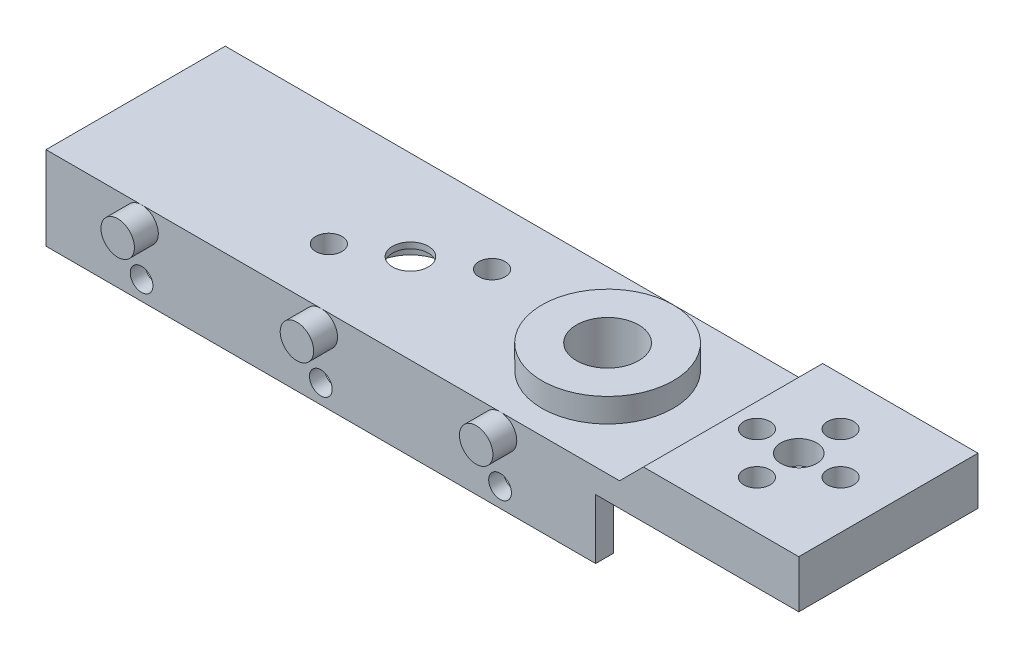
SolidWorks part; units mm, degrees
ref_plane "前视基准面" through (0, 0, 0) normal (0, 0, 1) x (1, 0, 0)
ref_plane "上视基准面" through (0, 0, 0) normal (0, 1, 0) x (1, 0, 0)
ref_plane "右视基准面" through (0, 0, 0) normal (1, 0, 0) x (0, 0, -1)
other "Configuration Table"
sketch "草图1" plane through (0, 0, 0) normal (0, 1, 0) x (1, 0, 0)
  line L0 (-31.5, 7.5) -> (31.5, 7.5)
  line L1 (31.5, 7.5) -> (31.5, -7.5)
  line L2 (31.5, -7.5) -> (-31.5, -7.5)
  line L3 (-31.5, -7.5) -> (-31.5, 7.5)
  line L4 (-31.5, 0) -> (31.5, 0) construction
  line L5 (-12.8301, -2.5) -> (-4.1699, 2.5) construction
  line L6 (-13.3083, -5.95) -> (-3.6917, -5.95) construction
  line L7 (-13.3083, 5.95) -> (-3.6917, 5.95) construction
  line L8 (-8.5, 0) -> (-8.5, 4.4384) construction
  line L10 (31.5, 7.5) -> (16.5, 7.5)
  line L11 (31.5, 7.5) -> (31.5, -7.5)
  line L12 (31.5, -7.5) -> (16.5, -7.5)
  line L13 (16.5, 7.5) -> (16.5, -7.5)
  circle A0 centre (-8.5, 0) radius 1.5
  circle A1 centre (-4.1699, 2.5) radius 1.1
  circle A3 centre (-12.8301, -2.5) radius 1.1
  arc A4 (-13.3083, 5.95) -> (-13.3083, -5.95) centre (-8.5, 0) ccw construction
  circle A5 centre (8, 0) radius 2.6
  arc A6 (-3.6917, -5.95) -> (-3.6917, 5.95) centre (-8.5, 0) ccw construction
  circle A7 centre (24, 0) radius 1.5
  circle A8 centre (24, 0) radius 3.5 construction
  circle A9 centre (27.5, 0) radius 1.1
  circle A10 centre (24, -3.5) radius 1.1
  circle A11 centre (20.5, 0) radius 1.1
  circle A12 centre (24, 3.5) radius 1.1
  circle A13 centre (-4.1699, -2.5) radius 1.1
  circle A14 centre (-12.8301, 2.5) radius 1.1
  circle A20 centre (24, 0) radius 6
  circle A21 centre (8, 0) radius 7
  point P5 (0, 7.5)
  point P7 (-31.5, 0)
  dimension "D3" = 3
  dimension "D6" = 2.2
  dimension "D9" = 15.3
  dimension "D12" = 5.2
  dimension "D14" = 3
  dimension "D15" = 7
  dimension "D16" = 2.2
  dimension "D22" = 12
  dimension "D23" = 14
  dimension "D1" = 63
  dimension "D2" = 15
  dimension "D4" = 23
  dimension "D7" = 30
  dimension "D8" = 10
  dimension "D10" = 11.9
  dimension "D11" = 16.5
  dimension "D13" = 16
  dimension "D21" = 15
  dimension "D5" = 2
  dimension "D17" = 4
extrude "凸台-拉伸1" add sketch "草图1" along normal blind 2
sketch "草图2" plane through (0, 0, 7.5) normal (0, 0, 1) x (1, 0, 0)
  line L0 (-31, 0.6) -> (31, 0.6) construction
  line L1 (-31.5, 2) -> (-31.5, 0) construction
  line L3 (31.5, 2) -> (-31.5, 2) construction
  circle A0 centre (-23.5, 0.6) radius 1.4
  circle A1 centre (-8.5, 0.6) radius 1.4
  circle A2 centre (6.5, 0.6) radius 1.4
  circle A3 centre (-23.5, -3.4) radius 0.95
  circle A4 centre (-8.5, -3.4) radius 0.95
  circle A5 centre (6.5, -3.4) radius 0.95
  line M13 (-31.5, 0) -> (31.5, 0)
  dimension "D1" = 2.8
  dimension "D2" = 2.8
  dimension "D3" = 2.8
  dimension "D8" = 1.9
  dimension "D4" = 15
  dimension "D5" = 15
  dimension "D6" = 8
  dimension "D7" = 1.4
  dimension "D9" = 4
  dimension "D10" = 3
extrude "凸台-拉伸2" add sketch "草图2" along normal blind 2 contours A0 L0 | L0 A0 M13 | A0 M13 | A1 L0 | L0 A1 M13 | A2 L0 | L0 A2 M13 | A2 M13 | A1 region at (-23.5, 1.1942, 7.5) region at (-23.5, 0.3049, 7.5) region at (-23.5, -0.3294, 7.5) region at (-8.5, 1.1942, 7.5) region at (-8.5, 0.3049, 7.5) region at (6.5, 1.1942, 7.5) region at (6.5, 0.3049, 7.5) region at (6.5, -0.3294, 7.5)
sketch "草图3" plane through (0, 0, 0) normal (0, -1, 0) x (1, 0, 0)
  circle A0 centre (-8.5, 0) radius 3
  dimension "D1" = 6
extrude "切除-拉伸1" cut sketch "草图3" against normal blind 1.5
sketch "草图4" plane through (0, 0, 0) normal (0, -1, 0) x (1, 0, 0)
  line L1 (-31.5, 7.5) -> (14.5, 7.5)
  line L2 (-31.5, 7.5) -> (-31.5, 6)
  line L3 (-31.5, 6) -> (14.5, 6)
  line L4 (14.5, 7.5) -> (14.5, 6)
  dimension "D1" = 46
  dimension "D2" = 1.5
extrude "凸台-拉伸3" add sketch "草图4" along normal blind 5
extrude "切除-拉伸2" cut sketch "草图2<3>" against normal up to surface (1.5 mm away) contours A3 | A4 | A5 up to face at (-8.5, -2.5, 6)
sketch "草图2<3>" plane through (0, 0, 7.5) normal (0, 0, 1) x (1, 0, 0) same geometry as "草图2"
sketch "草图5" plane through (0, 0, 6) normal (0, 0, -1) x (-1, 0, 0)
  line L0 (22.403, -1.5) -> (24.597, -1.5)
  line L1 (24.597, -1.5) -> (25.6939, -3.4)
  line L2 (25.6939, -3.4) -> (24.597, -5.3)
  line L3 (24.597, -5.3) -> (22.403, -5.3)
  line L4 (22.403, -5.3) -> (21.3061, -3.4)
  line L5 (21.3061, -3.4) -> (22.403, -1.5)
  line L6 (21.3061, -3.4) -> (25.6939, -3.4) construction
  line L7 (24.597, -1.5) -> (22.403, -5.3) construction
  line L8 (6.3061, -3.4) -> (7.403, -1.5)
  line L9 (7.403, -1.5) -> (9.597, -1.5)
  line L10 (9.597, -1.5) -> (10.6939, -3.4)
  line L11 (10.6939, -3.4) -> (9.597, -5.3)
  line L12 (9.597, -5.3) -> (7.403, -5.3)
  line L13 (7.403, -5.3) -> (6.3061, -3.4)
  line L14 (-8.6939, -3.4) -> (-7.597, -1.5)
  line L15 (-7.597, -1.5) -> (-5.403, -1.5)
  line L16 (-5.403, -1.5) -> (-4.3061, -3.4)
  line L17 (-4.3061, -3.4) -> (-5.403, -5.3)
  line L18 (-5.403, -5.3) -> (-7.597, -5.3)
  line L19 (-7.597, -5.3) -> (-8.6939, -3.4)
  line L20 (7.403, -1.5) -> (9.597, -5.3) construction
  line L21 (7.403, -5.3) -> (9.597, -1.5) construction
  circle A0 centre (23.5, -3.4) radius 0.95
  circle A1 centre (8.5, -3.4) radius 0.95
  circle A2 centre (8.5, -3.4) radius 0.95 construction
  circle A3 centre (23.5, -3.4) radius 0.95 construction
  point P17 (23.5, -3.4)
  dimension "D1" = 120
  dimension "D2" = 120
  dimension "D3" = 120
  dimension "D4" = 3.8
  dimension "D5" = 3.8
  dimension "D6" = 3.8
  dimension "D7" = 3
extrude "切除-拉伸3" cut sketch "草图5" against normal blind 0.25 contours L14 L15 L16 L17 L18 L19 | L8 L9 L10 L11 L12 L13 | L5 L0 L1 L2 L3 L4
extrude "凸台-拉伸4" add sketch "草图1<7>" along normal blind 4 contours L11 L10 L13 L12 | A12 | A9 | A10 | A7 | A11
sketch "草图1<7>" plane through (0, 0, 0) normal (0, 1, 0) x (1, 0, 0) same geometry as "草图1"
extrude "切除-拉伸4" cut sketch "草图1<8>" along normal blind 2 contours A20 A7 A9 A10 A11 A12 region at (18.1697, 0, 0)
sketch "草图1<8>" plane through (0, 0, 0) normal (0, 1, 0) x (1, 0, 0) same geometry as "草图1"
sketch "草图6" plane through (0, 0, -7.5) normal (0, 0, -1) x (-1, 0, 0)
  line L0 (-16.5, 2) -> (-18.5, 4)
  line L1 (-31.5, 4) -> (-16.5, 4) construction
  line L2 (-18.5, 4) -> (-16.5, 4)
  line L3 (-16.5, 4) -> (-16.5, 2) construction
  line L4 (-16.5, 4) -> (-16.5, 2)
  dimension "D1" = 45
extrude "切除-拉伸5" cut sketch "草图6" against normal up to surface (15 mm away) up to face at (1.0857, 0.7, 7.5)
sketch "草图8" plane through (0, 0, 0) normal (0, -1, 0) x (1, 0, 0)
  circle A0 centre (8, 0) radius 2.6
  circle A1 centre (8, 0) radius 5.5
  circle A2 centre (8, 0) radius 2.6 construction
  dimension "D1" = 11
extrude "凸台-拉伸11" add sketch "草图8" along normal blind 3
sketch "草图10" plane through (0, -3, 0) normal (0, -1, 0) x (1, 0, 0)
  line L0 (8, 0) -> (8, 4.0685) construction
  line L1 (8, 0) -> (4.0288, 0) construction
  line L2 (8, 3.1754) -> (5.25, 1.5877)
  line L3 (5.25, 1.5877) -> (5.25, -1.5877)
  line L4 (8, 3.1754) -> (10.75, 1.5877)
  line L5 (10.75, 1.5877) -> (10.75, -1.5877)
  line L6 (8, -3.1754) -> (10.75, -1.5877)
  line L7 (8, -3.1754) -> (5.25, -1.5877)
  circle A2 centre (8, 0) radius 2.6 construction
  point P1 (8, 2.0343)
  point P11 (8, 0)
  point P18 (10.75, 0)
  point P20 (5.25, 0)
  dimension "D1" = 120
  dimension "D2" = 5.5
  dimension "D3" = 5.5
extrude "切除-拉伸6" cut sketch "草图10" against normal blind 3.5
sketch "草图11" plane through (0, -3, 0) normal (0, -1, 0) x (1, 0, 0)
  line L0 (3.101, 2.5) -> (12.899, 2.5)
  line L1 (-31.5, 6) -> (14.5, 6) construction
  circle A0 centre (8, 0) radius 5.5 construction
  arc A1 (3.101, 2.5) -> (12.899, 2.5) centre (8, 0) cw
  dimension "D1" = 3.5
extrude "切除-拉伸7" cut sketch "草图11" against normal up to surface (3 mm away) up to face at (-4.1699, 0, -1.4)
extrude "凸台-拉伸12" add sketch "草图8<2>" against normal blind 4
sketch "草图8<2>" plane through (0, 0, 0) normal (0, -1, 0) x (1, 0, 0) same geometry as "草图8"
